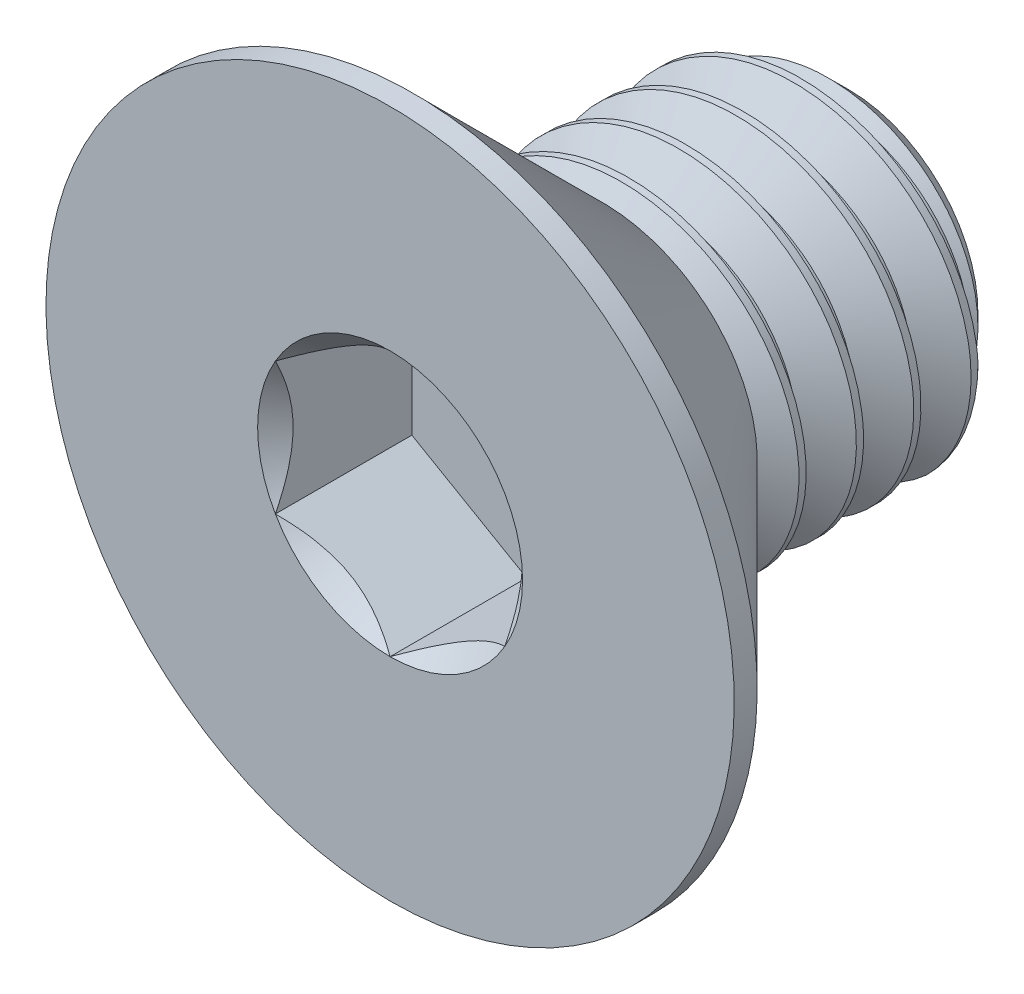
SolidWorks part; units mm, degrees
ref_plane "Front" through (0, 0, 0) normal (0, 0, 1) x (1, 0, 0)
ref_plane "Top" through (0, 0, 0) normal (0, 1, 0) x (1, 0, 0)
ref_plane "Right" through (0, 0, 0) normal (1, 0, 0) x (0, 0, -1)
sketch "Sketch1" plane through (0, 0, 0) normal (1, 0, 0) x (0, 0, -1)
  line L0 (0, 3) -> (0.2, 3) construction
  line L1 (0.2, 3) -> (1.7, 1.5) construction
  line L2 (0, 1.5) -> (4, 1.5)
  line L3 (4, 1.5) -> (4, 0)
  line L4 (4, 0) -> (0, 0)
  line L5 (0, 0) -> (0, 3) construction
  line L6 (0, 3) -> (0, -3) construction
  line L7 (4, 1.5) -> (4, -1.5) construction
  line L8 (0, -3) -> (0.2, -3) construction
  line L9 (0.2, -3) -> (1.7, -1.5) construction
  line L11 (0, 1.5) -> (0, 0)
  line L12 (1.7, 1.5) -> (1.7, 0) construction
  dimension "Head Ht" = 1.7
  dimension "Head Dia" = 6
  dimension "Dia" = 3
  dimension "Lg" = 4
  dimension "Head Angle" = 90
revolve "Revolve1" add sketch "Sketch1" angle 360 mid plane about L4
sketch "Sketch3" plane through (0, 0, -4) normal (0, 0, -1) x (-1, 0, 0)
  circle A0 centre (0, 0) radius 1.5
curve "Helix/Spiral1" pitch 0.5 height 4 radius 1.5 centre (0, 0, -4) axis (0, 0, 1) start towards (0, 1, 0)
sketch "Sketch2" plane through (0, 0, 0) normal (1, 0, 0) x (0, 0, -1)
  line L0 (4, 1.5) -> (4.4375, 1.5)
  line L1 (4.4375, 1.5) -> (4.25, 1.1752)
  line L2 (4.25, 1.1752) -> (4.1875, 1.1752)
  line L3 (4.1875, 1.1752) -> (4, 1.5)
  line L4 (4.0938, 1.3376) -> (4.3437, 1.3376) construction
  dimension "D1" = 60
  dimension "D2" = 0.0625
  dimension "D3" = 0.25
chamfer "Chamfer1" distance 0.375 angle 45 1 edges at (0, 1.5, -4)
sweep "Cut-Sweep1" cut profiles "Sketch2" path "Helix/Spiral1" align with end faces yes
sketch "Sketch7" plane through (0, 0, 0) normal (1, 0, 0) x (0, 0, -1)
  line L0 (0, 3) -> (0.2, 3) construction
  line L1 (0.2, 3) -> (1.7, 1.5) construction
  line L2 (0, 3) -> (0.2, 3)
  line L3 (0.2, 3) -> (1.7, 1.5)
  line L4 (1.7, 1.5) -> (1.7, 0) construction
  line L5 (1.7, 1.5) -> (1.7, 0)
  line L7 (0, 0) -> (0, 3) construction
  line L8 (0, 0) -> (0, 3)
  line L9 (0, 0) -> (1.7, 0)
  line L10 (3.3, 0) -> (-3.3, 0) construction
revolve "Revolve2" add sketch "Sketch7" angle 360 mid plane about L9
ref_plane "Plane1" through (0, 0, -1.7) normal (0, 0, 1) x (1, 0, 0)
sketch "Sketch8" plane through (0, 0, -1.7) normal (0, 0, 1) x (1, 0, 0)
  circle A0 centre (0, 0) radius 1.5
extrude "Boss-Extrude1" add sketch "Sketch8" against normal through all draft 45
sketch "Sketch5" plane through (0, 0, 0) normal (0, 0, 1) x (1, 0, 0)
  line L1 (1, -0.5774) -> (1, 0.5774)
  line L2 (1, 0.5774) -> (0, 1.1547)
  line L3 (0, 1.1547) -> (-1, 0.5774)
  line L4 (-1, 0.5774) -> (-1, -0.5774)
  line L5 (-1, -0.5774) -> (0, -1.1547)
  line L6 (0, -1.1547) -> (1, -0.5774)
  circle A0 centre (0, 0) radius 1 construction
  dimension "Hex" = 2
extrude "Cut-Extrude2" cut sketch "Sketch5" against normal blind 1.19
sketch "Sketch6" plane through (0, 0, 0) normal (0, 0, 1) x (1, 0, 0)
  circle A0 centre (0, 0) radius 1.1547
extrude "Cut-Extrude3" cut sketch "Sketch6" against normal blind 1.19 draft 45
sketch "Sketch9" [suppressed] plane through (0, 0, -5.5) normal (0, 0, 1) x (1, 0, 0)
  circle A1 centre (0, 0) radius 5
  circle A2 centre (0, 0) radius 5
  point P0 (0, 5)
  dimension "D1" = 0
extrude "Boss-Extrude2" [suppressed] add sketch "Sketch9" against normal offset from surface (18.5 mm away) 26 up to face at (0, 1.125, -4)
fillet "Fillet1" [suppressed] radius 0.3
sketch "Sketch10" plane through (0, 0, 0) normal (1, 0, 0) x (0, 0, -1)
  line L0 (4, 1.5) -> (4, -1.5) construction
  point P0 (3.25, -1.5)
  dimension "D1" = 0.75
equation "\"D3@Helix/Spiral1\" = \"Lg@Sketch1\""
equation "\"D2@Sketch2\" = \"D4@Helix/Spiral1\" * .125"
equation "\"D3@Sketch2\" = \"D4@Helix/Spiral1\" * .5"
equation "\"D1@Chamfer1\" = \"D4@Helix/Spiral1\" * .75"
equation "\"D1@Cut-Extrude2\" = \"Head Ht@Sketch1\" * .7"
equation "\"D1@Sketch10\" = \"D4@Helix/Spiral1\" * 1.5"
equation "\"D1@Cut-Extrude3\" = \"D1@Cut-Extrude2\""
equation "\"D1@Fillet1\" = \"Dia@Sketch1\" * .1"
